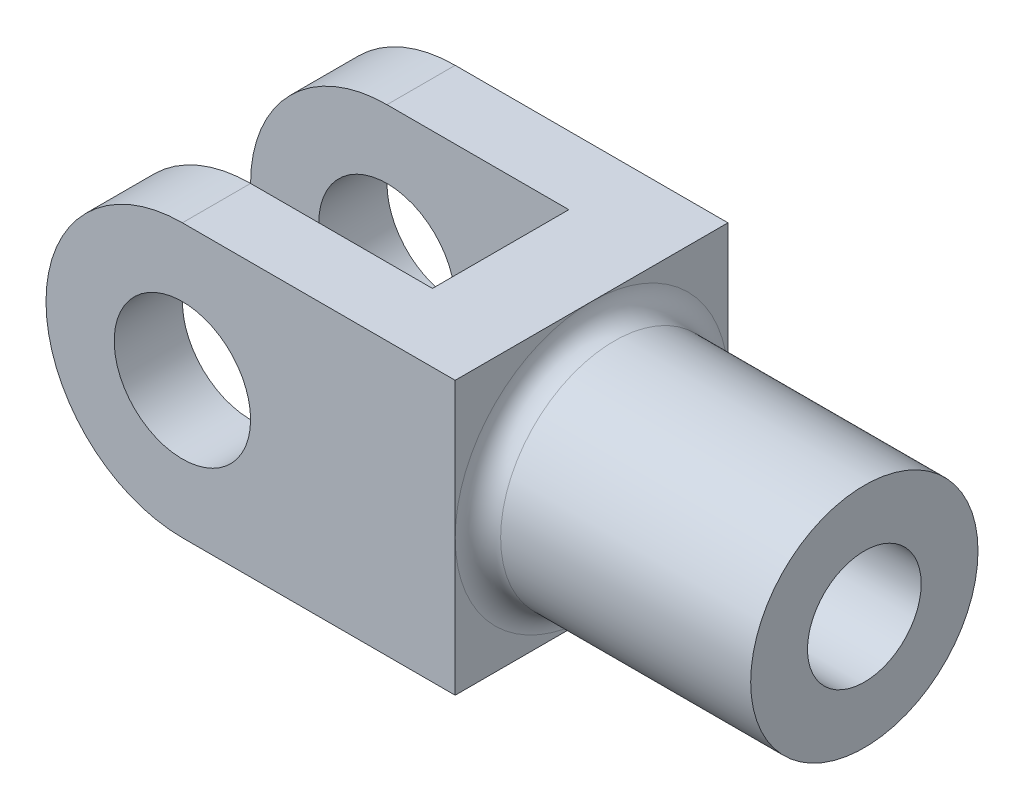
SolidWorks part; units mm, degrees
material "Plain Carbon Steel"
ref_plane "Front Plane" through (0, 0, 0) normal (0, 0, 1) x (1, 0, 0)
ref_plane "Top Plane" through (0, 0, 0) normal (0, 1, 0) x (1, 0, 0)
ref_plane "Right Plane" through (0, 0, 0) normal (1, 0, 0) x (0, 0, -1)
sketch "Sketch1" plane through (0, 0, 0) normal (0, 0, 1) x (1, 0, 0)
  line L0 (0, 0) -> (0, -50000) construction
  line L1 (0, 0) -> (50000, 0) construction
  line L2 (0, -6) -> (12, -6)
  line L3 (12, -6) -> (12, 6)
  line L4 (12, 6) -> (0, 6)
  circle A0 centre (0, 0) radius 3
  arc A1 (0, -6) -> (0, 6) centre (0, 0) cw
  point P12 (12, 0)
  dimension "D1" = 6
  dimension "D2" = 6
  dimension "D3" = 12
extrude "Boss-Extrude1" add sketch "Sketch1" along normal mid plane 12
sketch "Sketch2" plane through (0, 0, 0) normal (0, 1, 0) x (1, 0, 0)
  line L0 (0, 0) -> (-50000, 0) construction
  line L1 (-6, 6) -> (-6, -6) construction
  line L3 (8, 3) -> (-6, 3)
  line L4 (8, 3) -> (8, -3)
  line L5 (8, -3) -> (-6, -3)
  line L6 (-6, 3) -> (-6, -3)
  line L7 (8, 3) -> (-6, -3) construction
  line L8 (8, -3) -> (-6, 3) construction
  point P4 (1, 0)
  dimension "D1" = 6
  dimension "D2" = 14
extrude "Cut-Extrude1" cut sketch "Sketch2" against normal through all both and the other way through all
sketch "Sketch3" plane through (12, 0, 0) normal (1, 0, 0) x (0, 0, -1)
  circle A0 centre (0, 0) radius 5
  circle A1 centre (0, 0) radius 2.5
  dimension "D1" = 10
  dimension "5" = 5
extrude "Boss-Extrude2" add sketch "Sketch3" along normal blind 12 contours A0 A1 region at (12, 0, 4.8586)
cosmetic thread "Cosmetic Thread1" parameters "D2"=6
fillet "Fillet1" radius 1 1 edges at (12, 0, 5)
